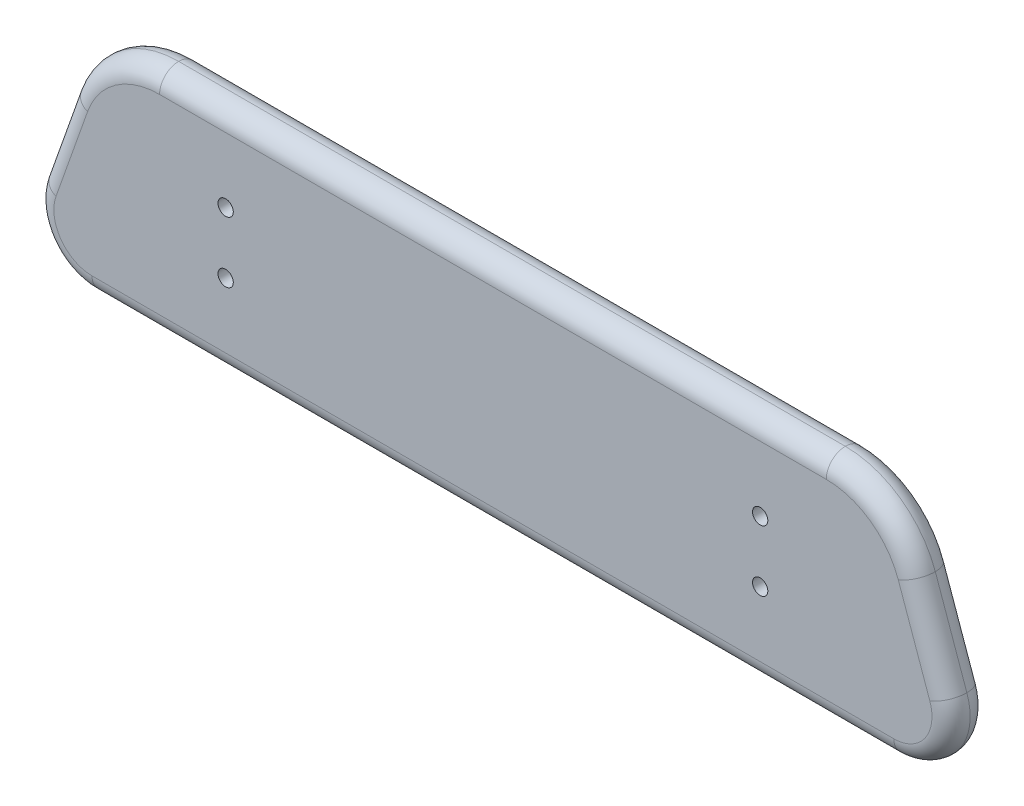
SolidWorks part; units mm, degrees
material "Oak"
ref_plane "Front" through (0, 0, 0) normal (0, 0, 1) x (1, 0, 0)
ref_plane "Top" through (0, 0, 0) normal (0, 1, 0) x (1, 0, 0)
ref_plane "Right" through (0, 0, 0) normal (1, 0, 0) x (0, 0, -1)
sketch "Sketch1" plane through (0, 0, 0) normal (0, 0, 1) x (1, 0, 0)
  line L0 (0, 0) -> (-105, 0)
  line L1 (-119.1396, 20.0071) -> (-110.8752, 43.3452)
  line L2 (-87.3091, 60) -> (87.3091, 60)
  line L3 (110.8752, 43.3452) -> (119.1396, 20.0071)
  line L4 (105, 0) -> (0, 0)
  arc A0 (-105, 0) -> (-119.1396, 20.0071) centre (-105, 15) cw
  arc A1 (-110.8752, 43.3452) -> (-87.3091, 60) centre (-87.3091, 35) cw
  arc A2 (87.3091, 60) -> (110.8752, 43.3452) centre (87.3091, 35) cw
  arc A3 (119.1396, 20.0071) -> (105, 0) centre (105, 15) cw
  point P14 (0, 60)
  dimension "D5" = 25
  dimension "D6" = 15
  dimension "D1" = 60
  dimension "D2" = 105
  dimension "D3" = 210
  dimension "D4" = 70.5
extrude "Boss-Extrude1" add sketch "Sketch1" along normal blind 10
sketch "Sketch2" plane through (0, 0, 10) normal (0, 0, 1) x (1, 0, 0)
  line L0 (-105, 0) -> (105, 0) construction
  line L1 (0, 0) -> (0, 60) construction
  line L2 (87.3091, 60) -> (-87.3091, 60) construction
  circle A0 centre (-70, 22) radius 2
  circle A1 centre (-70, 38) radius 2
  circle A2 centre (70, 22) radius 2
  circle A3 centre (70, 38) radius 2
  dimension "D4" = 4
  dimension "D1" = 22
  dimension "D2" = 38
  dimension "D3" = 70
extrude "Cut-Extrude1" cut sketch "Sketch2" against normal blind 8
fillet "Fillet1" radius 5 16 edges at (-117.2496, 6.3428, 0) (-115.0074, 31.6761, 0) (-101.7378, 55.416, 0) (0, 60, 0) (101.7378, 55.416, 0) (115.0074, 31.6761, 0) (117.2496, 6.3428, 0) (-117.2496, 6.3428, 10) (-115.0074, 31.6761, 10) (-101.7378, 55.416, 10) (0, 60, 10) (101.7378, 55.416, 10) (115.0074, 31.6761, 10) (117.2496, 6.3428, 10) (0, 0, 0) (0, 0, 10)
